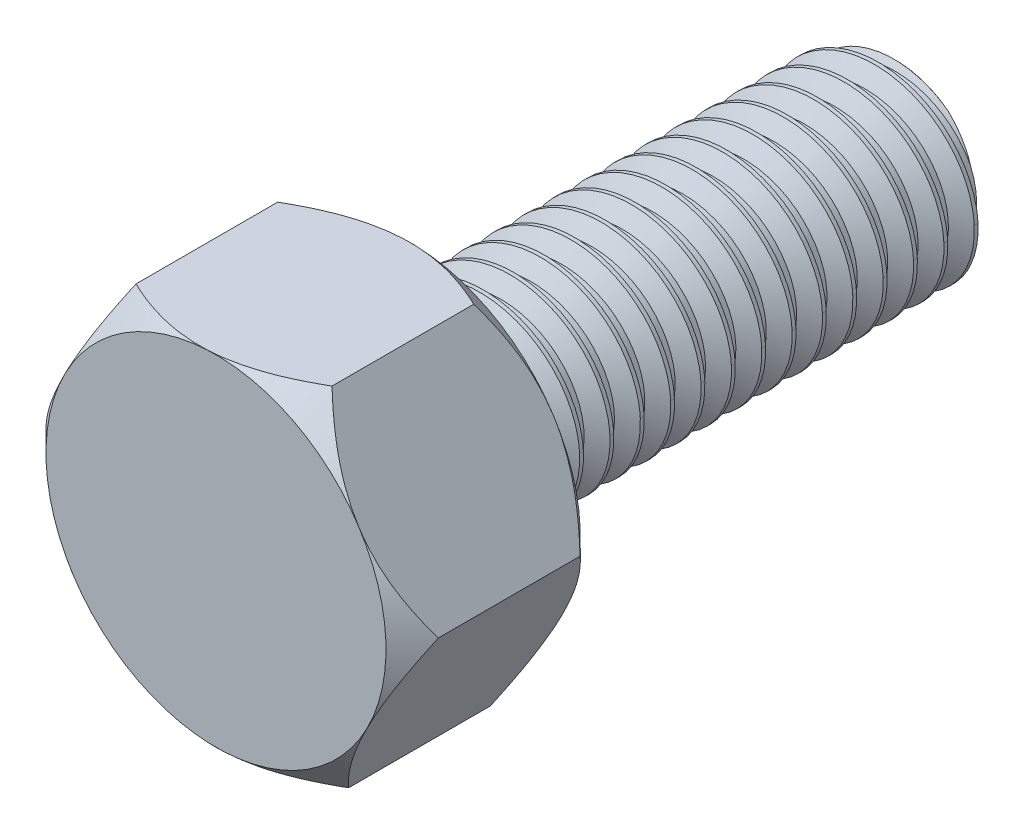
SolidWorks part; units mm, degrees
ref_plane "Front Plane" through (0, 0, 0) normal (0, 0, 1) x (1, 0, 0)
ref_plane "Top Plane" through (0, 0, 0) normal (0, 1, 0) x (1, 0, 0)
ref_plane "Right Plane" through (0, 0, 0) normal (1, 0, 0) x (0, 0, -1)
sketch "Sketch1" plane through (0, 0, 0) normal (0, 0, 1) x (1, 0, 0)
  line L1 (-3.694, -7.1894) -> (4.3792, -6.7938)
  line L2 (4.3792, -6.7938) -> (8.0732, 0.3956)
  line L3 (8.0732, 0.3956) -> (3.694, 7.1894)
  line L4 (3.694, 7.1894) -> (-4.3792, 6.7938)
  line L5 (-4.3792, 6.7938) -> (-8.0732, -0.3956)
  line L6 (-8.0732, -0.3956) -> (-3.694, -7.1894)
  circle A0 centre (0, 0) radius 7 construction
  dimension "D1" = 14
extrude "Boss-Extrude1" add sketch "Sketch1" along normal mid plane 8
sketch "Sketch2" plane through (0, 0, 4) normal (0, 0, 1) x (1, 0, 0)
  circle A0 centre (0, 0) radius 7
extrude "Cut-Extrude1" cut sketch "Sketch2" against normal through all draft 45 flip side to cut
mirror "Mirror1" about plane through (0, 0, 0) normal (0, 0, 1) of "Cut-Extrude1"
sketch "Sketch3" plane through (0, 0, -4) normal (0, 0, -1) x (-1, 0, 0)
  circle A0 centre (0, 0) radius 4
extrude "Boss-Extrude2" add sketch "Sketch3" along normal blind 20
chamfer "Chamfer1" distance 0.5 angle 45 1 edges at (-4, 0, -24)
thread "Thread1" pitch 1.25 method cut profile "Thread Profile1" start angle 0, offset 0.0001, length 0, pitch 1.25, diameter 8
ref_plane "Plane1" through (-4, 0, -4.0001) normal (0, -1, 0) x (-1, 0, 0)
sketch "Thread Profile1" plane through (-4, 0, -4.0001) normal (0, -1, 0) x (-1, 0, 0)
  line L0 (0, 0) -> (0, 1.25) construction
  line L11 (0, 0) -> (0, 1.0937)
  line L12 (0, 1.0937) -> (-0.6766, 0.7031)
  line L13 (-0.6766, 0.7031) -> (-0.6766, 0.3906)
  line L15 (-0.6766, 0.3906) -> (0, 0)
  line L17 (-0.6766, 0.5469) -> (0, 0.5469) construction
  point P2 (0, 0)
  dimension "Pitch" = 1.25
  dimension "Profile_Angle" = 60
  dimension "Profile_Land" = 0.3125
  dimension "Profile_Height" = 0.6766
sketch "Sketch11" plane through (0, 0, 0) normal (0, 1, 0) x (1, 0, 0)
  line L4 (-4, 4.0001) -> (-3.3234, 4.3907)
  line L5 (-3.3234, 4.3907) -> (-3.3234, 4.7032)
  line L6 (-3.3234, 4.7032) -> (-4, 5.0938)
  line L7 (-4, 5.0938) -> (-4, 4.0001)
  line L8 (-4, 4.0001) -> (-3.3234, 4.3907)
  line L9 (-3.3234, 4.3907) -> (-3.3234, 4.7032)
  line L10 (-3.3234, 4.7032) -> (-4, 5.0938)
  line L11 (-4, 5.0938) -> (-4, 4.0001)
  dimension "D1" = 0
extrude "Cut-Extrude2" cut sketch "Sketch11" against normal through all
